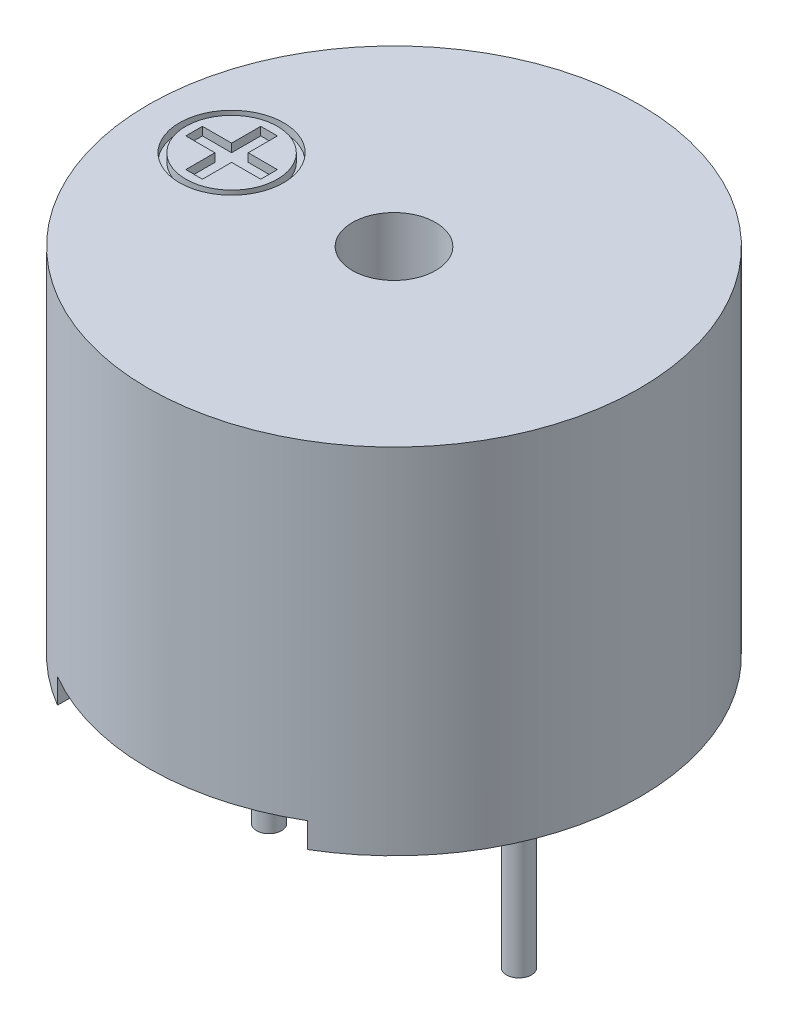
SolidWorks part; units mm, degrees
ref_plane "Alzado" through (0, 0, 0) normal (0, 0, 1) x (1, 0, 0)
ref_plane "Planta" through (0, 0, 0) normal (0, 1, 0) x (1, 0, 0)
ref_plane "Vista lateral" through (0, 0, 0) normal (1, 0, 0) x (0, 0, -1)
sketch "Sketch1" plane through (0, 0, 0) normal (0, 1, 0) x (1, 0, 0)
  circle A0 centre (0, 0) radius 5.9
  dimension "D1" = 11.8
extrude "Boss-Extrude1" add sketch "Sketch1" along normal blind 8.5
sketch "Sketch2" plane through (0, 0, 0) normal (0, -1, 0) x (1, 0, 0)
  line L0 (-3, 5.0804) -> (-3, -5.0804)
  line L2 (3, 5.0804) -> (3, -5.0804)
  circle A0 centre (0, 0) radius 5.9 construction
  arc A1 (-3, -5.0804) -> (3, -5.0804) centre (0, 0) ccw
  arc A2 (3, 5.0804) -> (-3, 5.0804) centre (0, 0) ccw
  dimension "D1" = 6
extrude "Cut-Extrude1" cut sketch "Sketch2" against normal blind 0.6
sketch "Sketch3" plane through (0, 0, 0) normal (0, -1, 0) x (1, 0, 0)
  circle A0 centre (0, 0) radius 5
  dimension "D1" = 10
extrude "Cut-Extrude2" cut sketch "Sketch3" against normal blind 2
sketch "Sketch4" plane through (0, 8.5, 0) normal (0, 1, 0) x (1, 0, 0)
  circle A0 centre (0, 0) radius 1
  dimension "D1" = 2
extrude "Cut-Extrude3" cut sketch "Sketch4" against normal blind 3
sketch "Sketch5" plane through (0, 8.5, 0) normal (0, 1, 0) x (1, 0, 0)
  line L0 (-4.1, 0.2) -> (-4.8, 0.2)
  line L1 (-3.7, -0.9) -> (-4.1, -0.9)
  line L2 (-3.7, -0.9) -> (-3.7, -0.2)
  line L3 (-3.7, 0.9) -> (-4.1, 0.9)
  line L4 (-4.1, -0.9) -> (-4.1, -0.2)
  line L5 (-3.7, -0.9) -> (-4.1, 0.9) construction
  line L6 (-3.7, 0.9) -> (-4.1, -0.9) construction
  line L7 (-3, 0.2) -> (-3.7, 0.2)
  line L8 (-3, 0.2) -> (-3, -0.2)
  line L9 (-3, -0.2) -> (-3.7, -0.2)
  line L10 (-4.8, 0.2) -> (-4.8, -0.2)
  line L11 (-3, 0.2) -> (-4.8, -0.2) construction
  line L12 (-3, -0.2) -> (-4.8, 0.2) construction
  line L13 (-4.1, -0.2) -> (-4.8, -0.2)
  line L14 (-3.7, 0.2) -> (-3.7, 0.9)
  line L15 (-4.1, 0.2) -> (-4.1, 0.9)
  circle A0 centre (-3.9, 0) radius 1.1
  circle A1 centre (-3.9, 0) radius 1.25
  dimension "D1" = 2.5
  dimension "D2" = 2.2
  dimension "D3" = 3.9
  dimension "D4" = 0.4
  dimension "D5" = 0.7
extrude "Cut-Extrude4" cut sketch "Sketch5" against normal blind 0.2 contours A1 A0 | L15 L3 L14 L7 L8 L9 L2 L1 L4 L13 L10 L0 region at (-5.1146, 8.5, 0)
sketch "Sketch6" plane through (0, 2, 0) normal (0, -1, 0) x (1, 0, 0)
  line L0 (-3, 0) -> (0, 0) construction
  line L1 (0, 0) -> (3, 0) construction
  circle A0 centre (-3, 0) radius 0.3
  circle A1 centre (3, 0) radius 0.3
  dimension "D2" = 0.6
  dimension "D1" = 6
extrude "Boss-Extrude2" add sketch "Sketch6" along normal blind 7
